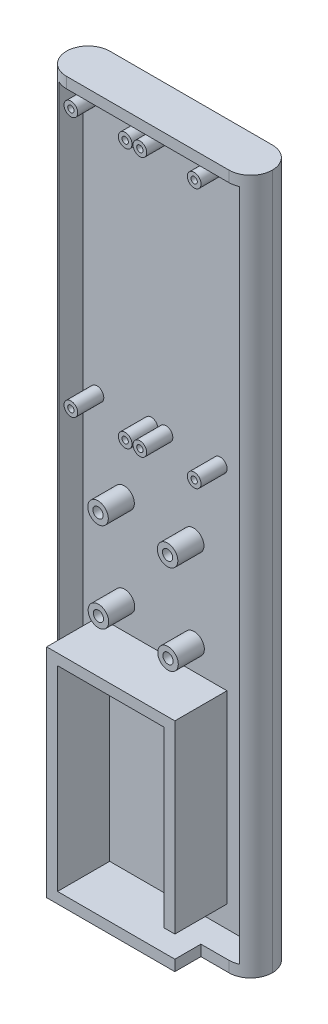
SolidWorks part; units mm, degrees
ref_plane "Front Plane" through (0, 0, 0) normal (0, 0, 1) x (1, 0, 0)
ref_plane "Top Plane" through (0, 0, 0) normal (0, 1, 0) x (1, 0, 0)
ref_plane "Right Plane" through (0, 0, 0) normal (1, 0, 0) x (0, 0, -1)
sketch "Sketch1" plane through (0, 0, 0) normal (0, 0, 1) x (1, 0, 0)
  line L1 (88.9, 0) -> (152.4, 0)
  line L2 (88.9, 0) -> (88.9, 203.2)
  line L3 (88.9, 203.2) -> (152.4, 203.2)
  line L4 (152.4, 0) -> (152.4, 203.2)
  dimension "D1" = 63.5
  dimension "D2" = 203.2
extrude "Boss-Extrude1" add sketch "Sketch1" along normal blind 5.08
sketch "Sketch2" plane through (0, 0, 5.08) normal (0, 0, 1) x (1, 0, 0)
  line L4 (152.4, 203.2) -> (88.9, 203.2) construction
  line L5 (152.4, 0) -> (152.4, 203.2) construction
  line L6 (123.8316, 195.58) -> (138.7, 195.58)
  line L7 (123.8316, 195.58) -> (123.8316, 120.6787)
  line L8 (123.8316, 119.6787) -> (139.7, 119.6787)
  line L9 (139.7, 194.58) -> (139.7, 120.6787)
  line L10 (103.6632, 119.6787) -> (119.5316, 119.6787)
  line L11 (103.6632, 195.58) -> (118.5316, 195.58)
  line L12 (103.6632, 195.58) -> (103.6632, 120.6787)
  line L13 (119.5316, 194.58) -> (119.5316, 120.6787)
  circle A9 centre (123.8316, 195.58) radius 0.925
  circle A10 centre (123.8316, 195.58) radius 2
  circle A11 centre (139.7, 195.58) radius 0.925
  circle A12 centre (139.7, 195.58) radius 2
  circle A13 centre (123.8316, 119.6787) radius 0.925
  circle A14 centre (123.8316, 119.6787) radius 2
  circle A15 centre (139.7, 119.6787) radius 2
  circle A16 centre (139.7, 119.6787) radius 0.925
  circle A17 centre (103.6632, 119.6787) radius 0.925
  circle A18 centre (119.5316, 119.6787) radius 0.925
  circle A19 centre (119.5316, 195.58) radius 2
  circle A20 centre (103.6632, 195.58) radius 0.925
  circle A21 centre (119.5316, 195.58) radius 0.925
  circle A22 centre (103.6632, 119.6787) radius 2
  circle A23 centre (103.6632, 195.58) radius 2
  circle A24 centre (119.5316, 119.6787) radius 2
  point P0 (139.7, 195.58)
  point P5 (119.5316, 119.6787)
  point P6 (119.5316, 195.58)
  dimension "D2" = 7.62
  dimension "D7" = 4.3
  dimension "D5" = 4
  dimension "D6" = 1.85
  dimension "D9" = 1.85
  dimension "D11" = 1.85
  dimension "D12" = 1.85
  dimension "D13" = 1.85
  dimension "D14" = 1.85
  dimension "D15" = 1.85
  dimension "D16" = 1.85
  dimension "D3" = 12.7
  dimension "D4" = 1
  dimension "D8" = 1
  dimension "D10" = 75.9013
extrude "Boss-Extrude2" add sketch "Sketch2" along normal blind 7.62
sketch "Sketch3" plane through (0, 0, 5.08) normal (0, 0, 1) x (1, 0, 0)
  line L0 (152.4, 0) -> (141.6706, 0)
  line L1 (107.3806, 3.175) -> (107.3806, 60.325)
  line L2 (107.3806, 3.175) -> (138.4956, 3.175)
  line L3 (138.4956, 3.175) -> (138.4956, 60.325)
  line L4 (107.3806, 60.325) -> (138.4956, 60.325)
  line L5 (88.9, 0) -> (152.4, 0) construction
  line L7 (107.3806, 3.175) -> (104.2056, 0)
  line L9 (138.4956, 60.325) -> (141.6706, 63.5)
  line L10 (104.2056, 0) -> (104.2056, 63.5)
  line L11 (104.2056, 0) -> (141.6706, 0)
  line L12 (141.6706, 0) -> (141.6706, 63.5)
  line L13 (104.2056, 63.5) -> (141.6706, 63.5)
  dimension "D1" = 31.115
  dimension "D2" = 57.15
  dimension "D4" = 3.175
  dimension "D5" = 3.175
  dimension "D6" = 3.175
  dimension "D7" = 3.175
extrude "Boss-Extrude3" add sketch "Sketch3" along normal blind 15.24 contours L11 L12 L9 L3 L2 L7 | L13 L10 L7 L1 L4 L9
sketch "Sketch4" plane through (0, 0, 20.32) normal (0, 0, 1) x (1, 0, 0)
  line L0 (138.4956, 3.175) -> (138.4956, 60.325) construction
  line L5 (138.4956, 3.175) -> (138.4956, 9.525)
  line L6 (138.4956, 3.175) -> (141.6706, 3.175)
  line L7 (141.6706, 3.175) -> (141.6706, 9.525)
  line L8 (138.4956, 9.525) -> (141.6706, 9.525)
  line L9 (141.6706, 0) -> (141.6706, 63.5) construction
extrude "Cut-Extrude1" cut sketch "Sketch4" against normal blind 15.24
sketch "Sketch5" plane through (0, 0, 5.08) normal (0, 0, 1) x (1, 0, 0)
  line L0 (104.5882, 119.6787) -> (118.6066, 119.6787)
  circle A0 centre (111.5974, 97.3631) radius 1.5
  circle A1 centre (111.5974, 97.3631) radius 3
  circle A2 centre (131.9257, 96.8221) radius 1.5
  circle A3 centre (131.9257, 96.8221) radius 3
  circle A4 centre (111.7159, 71.2493) radius 1.5
  circle A5 centre (132.0538, 70.7084) radius 3
  circle A6 centre (111.7159, 71.2493) radius 3
  circle A7 centre (132.0538, 70.7084) radius 1.5
  circle A8 centre (103.6632, 119.6787) radius 0.925 construction
  circle A9 centre (103.6632, 119.6787) radius 0.925 construction
  circle A10 centre (119.5316, 119.6787) radius 0.925 construction
  circle A11 centre (119.5316, 119.6787) radius 0.925 construction
  point P7 (132.0539, 70.7047)
  dimension "D1" = 3
  dimension "D2" = 6
  dimension "D3" = 3
  dimension "D4" = 6
  dimension "D5" = 20.3355
  dimension "D8" = 26.114
  dimension "D9" = 26.114
extrude "Boss-Extrude4" add sketch "Sketch5" along normal blind 7.62 contours A3 A2 | A1 A0 | A6 A4 | A5 A7
sketch "Sketch8" plane through (0, 0, 5.08) normal (0, 0, 1) x (1, 0, 0)
  line L0 (88.9, 203.2) -> (88.9, 0) construction
  line L1 (152.4, 203.2) -> (88.9, 203.2)
  line L2 (152.4, 203.2) -> (152.4, 200.025)
  line L3 (152.4, 200.025) -> (88.9, 200.025)
  line L4 (88.9, 203.2) -> (88.9, 200.025)
  line L7 (104.2056, 0) -> (88.9, 0)
  line L8 (104.2056, 0) -> (104.2056, 3.175)
  line L9 (104.2056, 3.175) -> (88.9, 3.175)
  line L10 (88.9, 0) -> (88.9, 3.175)
  line L11 (141.6706, 3.175) -> (152.4, 3.175)
  line L12 (141.6706, 3.175) -> (141.6706, 0)
  line L13 (141.6706, 0) -> (152.4, 0)
  line L14 (152.4, 3.175) -> (152.4, 0)
  dimension "D1" = 3.175
  dimension "D2" = 3.175
extrude "Boss-Extrude5" add sketch "Sketch8" along normal blind 7.62
sketch "Sketch9" plane through (0, 0, 12.7) normal (0, 0, 1) x (1, 0, 0)
  line L1 (152.4, 203.2) -> (88.9, 203.2) construction
  line L2 (88.9, 0) -> (104.2056, 0) construction
  line L4 (96.012, 203.2) -> (88.9, 203.2)
  line L5 (96.012, 203.2) -> (96.012, 0)
  line L6 (96.012, 0) -> (88.9, 0)
  line L7 (88.9, 203.2) -> (88.9, 0)
  dimension "D1" = 7.112
extrude "Cut-Extrude2" cut sketch "Sketch9" against normal through all
sketch "Sketch10" plane through (0, 0, 5.08) normal (0, 0, 1) x (1, 0, 0)
  line L0 (96.012, 200.025) -> (152.4, 200.025) construction
  line L1 (96.012, 3.175) -> (99.568, 3.175)
  line L2 (96.012, 3.175) -> (96.012, 200.025)
  line L3 (96.012, 200.025) -> (99.568, 200.025)
  line L4 (99.568, 3.175) -> (99.568, 200.025)
  dimension "D1" = 3.556
extrude "Boss-Extrude6" add sketch "Sketch10" along normal up to vertex
sketch "Sketch11" plane through (152.4, 0, 0) normal (1, 0, 0) x (0, 0, -1)
  line L1 (0, 0) -> (-12.7, 0)
  line L2 (0, 0) -> (0, 203.2)
  line L3 (0, 203.2) -> (-12.7, 203.2)
  line L4 (-12.7, 0) -> (-12.7, 203.2)
extrude "Boss-Extrude7" add sketch "Sketch11" along normal blind 3.81
fillet "Fillet1" radius 6.35 4 edges at (156.21, 101.6, 12.7) (156.21, 101.6, 0) (96.012, 101.6, 0) (96.012, 101.6, 12.7)
